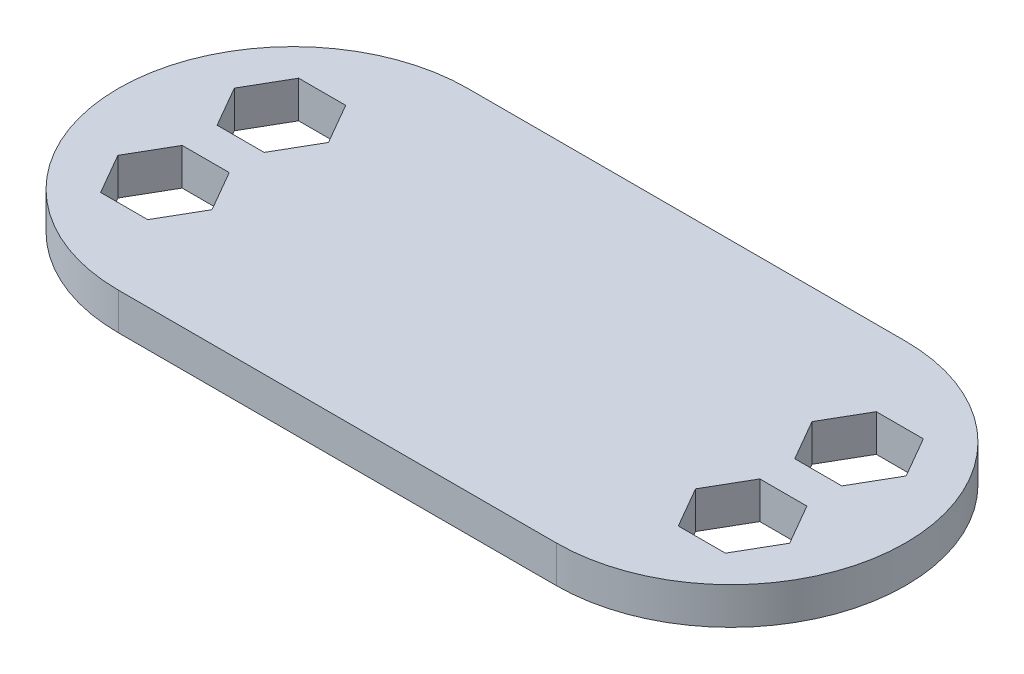
SolidWorks part; units mm, degrees
ref_plane "Front Plane" through (0, 0, 0) normal (0, 0, 1) x (1, 0, 0)
ref_plane "Top Plane" through (0, 0, 0) normal (0, 1, 0) x (1, 0, 0)
ref_plane "Right Plane" through (0, 0, 0) normal (1, 0, 0) x (0, 0, -1)
sketch "Sketch2" plane through (0, 0, 0) normal (0, 1, 0) x (1, 0, 0)
  line L0 (-145.5214, 0.9971) -> (-107.9214, 0.9971)
  line L2 (-145.5214, -29.0029) -> (-107.9214, -29.0029)
  line L4 (-151.5214, 3.0634) -> (-151.5214, -29.2944) construction
  line L9 (-101.9214, 1.8989) -> (-101.9214, -30.7894) construction
  line L10 (-126.7214, 0.9971) -> (-126.7214, -29.0029) construction
  line L11 (-149.5007, -12.5029) -> (-147.48, -9.0029)
  line L12 (-147.48, -9.0029) -> (-149.5007, -5.5029)
  line L13 (-149.5007, -5.5029) -> (-153.5421, -5.5029)
  line L14 (-153.5421, -5.5029) -> (-155.5629, -9.0029)
  line L15 (-155.5629, -9.0029) -> (-153.5421, -12.5029)
  line L16 (-153.5421, -12.5029) -> (-149.5007, -12.5029)
  line L17 (-160.5214, -14.0029) -> (-126.7214, -14.0029) construction
  line L18 (-153.5421, -15.5029) -> (-149.5007, -15.5029)
  line L19 (-155.5629, -19.0029) -> (-153.5421, -15.5029)
  line L20 (-153.5421, -22.5029) -> (-155.5629, -19.0029)
  line L21 (-149.5007, -22.5029) -> (-153.5421, -22.5029)
  line L22 (-147.48, -19.0029) -> (-149.5007, -22.5029)
  line L23 (-149.5007, -15.5029) -> (-147.48, -19.0029)
  line L24 (-103.9421, -15.5029) -> (-105.9629, -19.0029)
  line L25 (-105.9629, -19.0029) -> (-103.9421, -22.5029)
  line L26 (-103.9421, -22.5029) -> (-99.9007, -22.5029)
  line L27 (-99.9007, -22.5029) -> (-97.88, -19.0029)
  line L28 (-97.88, -19.0029) -> (-99.9007, -15.5029)
  line L29 (-99.9007, -15.5029) -> (-103.9421, -15.5029)
  line L30 (-99.9007, -12.5029) -> (-103.9421, -12.5029)
  line L31 (-97.88, -9.0029) -> (-99.9007, -12.5029)
  line L32 (-99.9007, -5.5029) -> (-97.88, -9.0029)
  line L33 (-103.9421, -5.5029) -> (-99.9007, -5.5029)
  line L34 (-105.9629, -9.0029) -> (-103.9421, -5.5029)
  line L35 (-103.9421, -12.5029) -> (-105.9629, -9.0029)
  arc A0 (-145.5214, 0.9971) -> (-145.5214, -29.0029) centre (-145.5214, -14.0029) ccw
  arc A7 (-107.9214, -29.0029) -> (-107.9214, 0.9971) centre (-107.9214, -14.0029) ccw
  circle A8 centre (-151.5214, -9.0029) radius 3.5 construction
  circle A9 centre (-151.5214, -19.0029) radius 3.5 construction
  circle A10 centre (-101.9214, -19.0029) radius 3.5 construction
  circle A11 centre (-101.9214, -9.0029) radius 3.5 construction
  dimension "D5" = 24.8
  dimension "D4" = 7
  dimension "D1" = 30
  dimension "D2" = 6
  dimension "D3" = 5
  dimension "D9" = 6
  dimension "D10" = 0
extrude "Boss-Extrude1" add sketch "Sketch2" along normal blind 3.175
